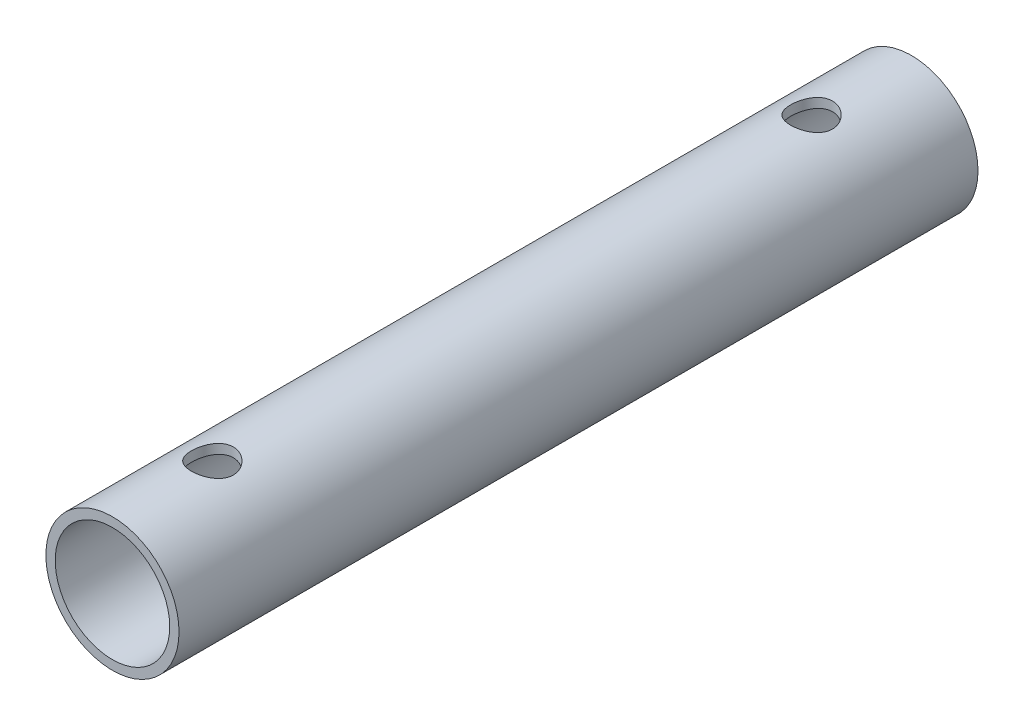
SolidWorks part; units mm, degrees
ref_plane "Front" through (0, 0, 0) normal (0, 0, 1) x (1, 0, 0)
ref_plane "Top" through (0, 0, 0) normal (0, 1, 0) x (1, 0, 0)
ref_plane "Right" through (0, 0, 0) normal (1, 0, 0) x (0, 0, -1)
sketch "Sketch1" plane through (0, 0, 0) normal (0, 0, 1) x (1, 0, 0)
  circle A0 centre (0, 0) radius 6.35
  circle A1 centre (0, 0) radius 5.461
extrude "Extrude1" add sketch "Sketch1" along normal blind 76.2
sketch "Sketch2" plane through (0, 0, 0) normal (0, 1, 0) x (1, 0, 0)
  line L0 (0, 0) -> (0, -9.525)
  line L1 (0, -76.2) -> (0, -66.675)
  line L2 (-6.35, -76.2) -> (6.35, -76.2) construction
  circle A0 centre (0, -9.525) radius 2
  circle A1 centre (0, -66.675) radius 2
extrude "Cut-Extrude1" cut sketch "Sketch2" against normal blind 38.1 and the other way blind 38.1
